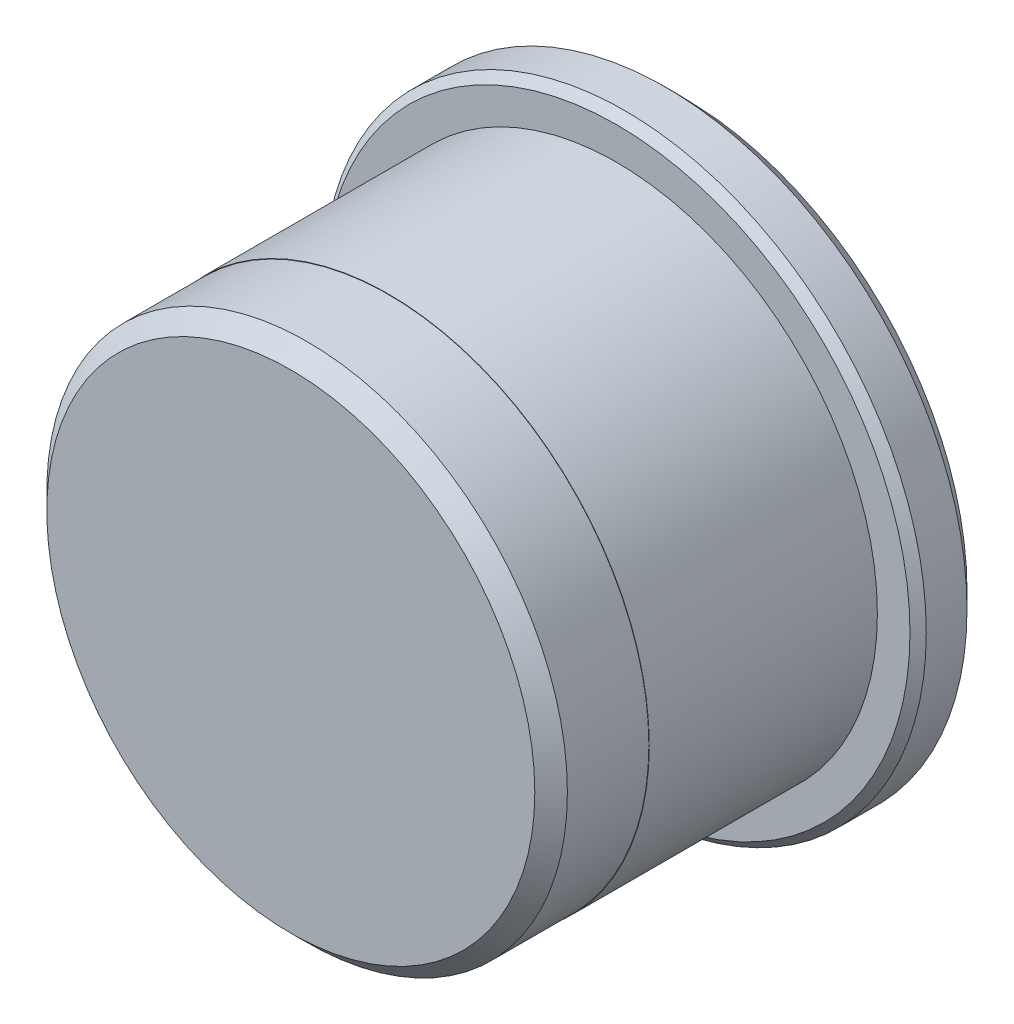
SolidWorks part; units mm, degrees
material "AISI 4140"
ref_plane "Front Plane" through (0, 0, 0) normal (0, 0, 1) x (1, 0, 0)
ref_plane "Top Plane" through (0, 0, 0) normal (0, 1, 0) x (1, 0, 0)
ref_plane "Right Plane" through (0, 0, 0) normal (1, 0, 0) x (0, 0, -1)
sketch "Sketch1" plane through (0, 0, 0) normal (1, 0, 0) x (0, 0, -1)
  line L0 (0, 0) -> (24, 0) construction
  line L1 (0, 0) -> (0, 14.975)
  line L2 (0, 14.975) -> (1, 15.975)
  line L3 (1, 15.975) -> (6, 15.975)
  line L4 (6, 15.975) -> (6, 16)
  line L5 (6, 16) -> (20, 16)
  line L6 (20, 16) -> (20, 18)
  line L7 (20, 18) -> (20.5, 18.5)
  line L8 (20.5, 18.5) -> (23, 18.5)
  line L9 (23, 18.5) -> (24, 17.5)
  line L10 (24, 17.5) -> (24, 14.0774)
  line L11 (24, 14.0774) -> (23, 13.5)
  line L12 (23, 13.5) -> (9, 13.5)
  line L13 (7, 13.75) -> (7, 11)
  line L14 (7, 11) -> (5, 11)
  line L15 (5, 11) -> (5, 1.5)
  line L16 (5, 1.5) -> (4.0987, 0)
  line L17 (4.0987, 0) -> (0, 0)
  line L18 (9, 13.5) -> (9, 13.75)
  line L19 (9, 13.75) -> (7, 13.75)
  dimension "D1" = 24
  dimension "D2" = 45
  dimension "D3" = 1
  dimension "D4" = 59
  dimension "D5" = 1.5
  dimension "D6" = 45
  dimension "D7" = 0.5
  dimension "D8" = 45
  dimension "D9" = 1
  dimension "D10" = 30
  dimension "D11" = 1
  dimension "D12" = 16
  dimension "D13" = 15.975
  dimension "D14" = 18.5
  dimension "D15" = 13.5
  dimension "D16" = 11
  dimension "D17" = 17
  dimension "D18" = 19
  dimension "D19" = 6
  dimension "D21" = 2
  dimension "D22" = 13.75
  dimension "D23" = 4
revolve "Revolve2" add sketch "Sketch1" angle 360 about L0
sketch "Sketch2" plane through (0, 0, 0) normal (0, 1, 0) x (0, 0, -1)
  line L1 (24, -17.5) -> (24, 17.5) construction
  circle A1 centre (27.3, 0) radius 4
  dimension "D2" = 0.7
  dimension "D1" = 8
extrude "Cut-Extrude3" cut sketch "Sketch2" along normal through all contours A1
pattern_circular "CirPattern1" count 3 over 360 about axis through (0, 0, -4.0987) along (0, 0, 1) of "Cut-Extrude3" reverse direction yes
